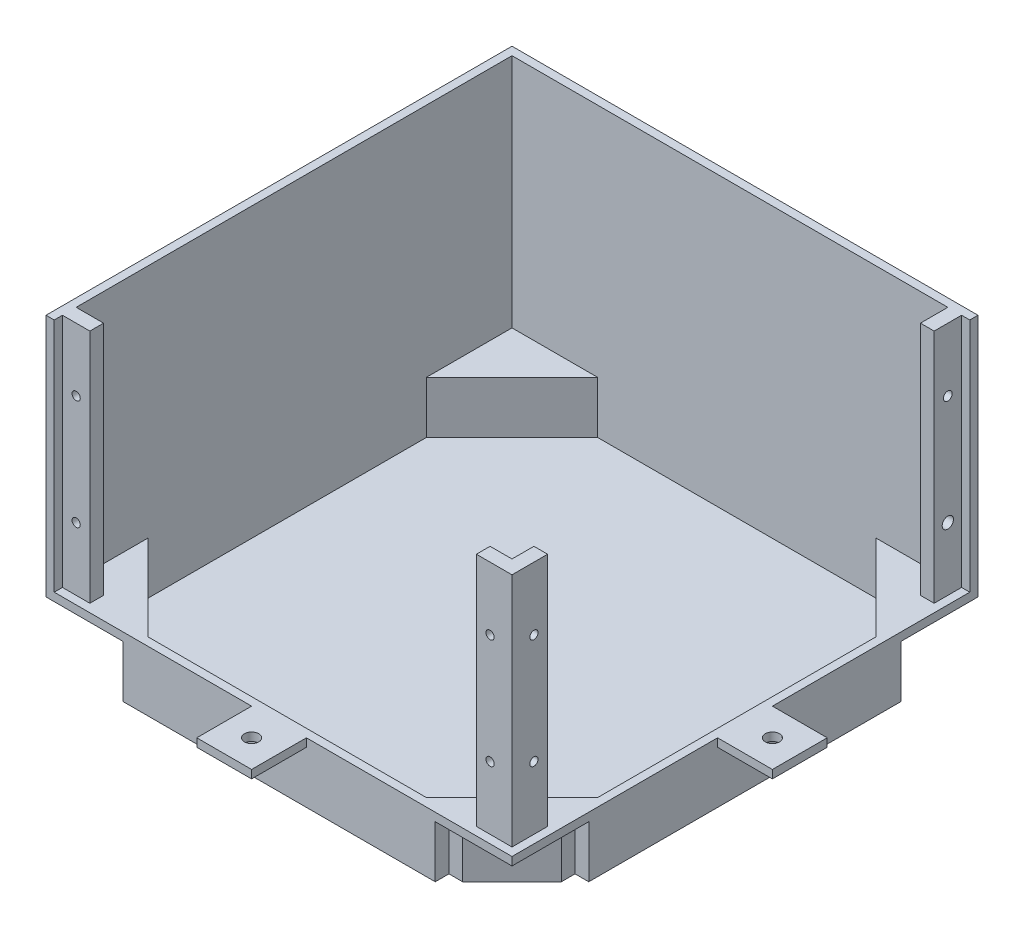
SolidWorks part; units mm, degrees
ref_plane "前视基准面" through (0, 0, 0) normal (0, 0, 1) x (1, 0, 0)
ref_plane "上视基准面" through (0, 0, 0) normal (0, 1, 0) x (1, 0, 0)
ref_plane "右视基准面" through (0, 0, 0) normal (1, 0, 0) x (0, 0, -1)
other "Configuration Table"
sketch "草图1" plane through (0, 0, 0) normal (0, 1, 0) x (1, 0, 0)
  line L21 (-80, 62) -> (-62, 80)
  line L23 (-85, 57) -> (-85, -57)
  line L26 (-85, 57) -> (-80, 57)
  line L27 (-80, 57) -> (-80, 62)
  line L28 (-57, 85) -> (-57, 80)
  line L30 (85, 57) -> (80, 57)
  line L31 (80, 57) -> (80, 62)
  line L33 (85, -57) -> (80, -57)
  line L34 (80, -57) -> (80, -62)
  line L37 (-85, -57) -> (-80, -57)
  line L38 (-80, -57) -> (-80, -62)
  line L39 (-57, 80) -> (-62, 80)
  line L40 (-57, 85) -> (57, 85)
  line L42 (57, 85) -> (57, 80)
  line L43 (57, 80) -> (62, 80)
  line L44 (62, 80) -> (80, 62)
  line L45 (-57, -85) -> (-57, -80)
  line L46 (-57, -80) -> (-62, -80)
  line L47 (57, -85) -> (57, -80)
  line L48 (57, -80) -> (62, -80)
  line L49 (-80, -62) -> (-62, -80)
  line L50 (85, 57) -> (85, -57)
  line L51 (62, -80) -> (80, -62)
  line L52 (-57, -85) -> (57, -85)
extrude "凸台-拉伸1" add sketch "草图1" along normal blind 4 contours L50 L33 L34 L51 L48 L47 L52 L45 L46 L49 L38 L37 L23 L26 L27 L21 L39 L28 L40 L42 L43 L44 L31 L30
sketch "草图2" plane through (0, 4, 0) normal (0, 1, 0) x (1, 0, 0)
  line L0 (-57, 85) -> (57, 85)
  line L1 (57, 85) -> (57, 80)
  line L2 (57, 80) -> (62, 80)
  line L3 (62, 80) -> (80, 62)
  line L4 (80, 62) -> (80, 57)
  line L5 (80, 57) -> (85, 57)
  line L6 (85, 57) -> (85, -57)
  line L7 (85, -57) -> (80, -57)
  line L8 (80, -57) -> (80, -62)
  line L9 (80, -62) -> (62, -80)
  line L10 (62, -80) -> (57, -80)
  line L11 (57, -80) -> (57, -85)
  line L12 (57, -85) -> (-57, -85)
  line L13 (-57, -85) -> (-57, -80)
  line L14 (-57, -80) -> (-62, -80)
  line L15 (-62, -80) -> (-80, -62)
  line L16 (-80, -62) -> (-80, -57)
  line L17 (-80, -57) -> (-85, -57)
  line L18 (-85, -57) -> (-85, 57)
  line L19 (-85, 57) -> (-80, 57)
  line L20 (-80, 57) -> (-80, 62)
  line L21 (-80, 62) -> (-62, 80)
  line L22 (-62, 80) -> (-57, 80)
  line L23 (-57, 80) -> (-57, 85)
  line L24 (-82, 50.7574) -> (-50.7574, 82)
  line L25 (50.7574, 82) -> (82, 50.7574)
  line L26 (50.7574, -82) -> (82, -50.7574)
  line L28 (-82, 50.7574) -> (-82, -50.7574)
  line L29 (50.7574, 82) -> (-50.7574, 82)
  line L30 (-82, -50.7574) -> (-50.7574, -82)
  line L31 (82, 50.7574) -> (82, -50.7574)
  line L32 (-50.7574, -82) -> (50.7574, -82)
extrude "凸台-拉伸2" add sketch "草图2" along normal blind 16 contours L23 L0 L1 L2 L3 L4 L5 L6 L7 L8 L9 L10 L11 L12 L13 L14 L15 L16 L17 L18 L19 L20 L21 L22 | L26 L31 L25 L29 L24 L28 L30 L32
sketch "草图3" plane through (0, 0, 0) normal (0, -1, 0) x (-1, 0, 0)
  line L0 (57, -85) -> (85, -85)
  line L1 (-57, 85) -> (-85, 85)
  line L3 (85, -85) -> (-85, -85)
  line L4 (85, -85) -> (85, 85)
  line L5 (85, 85) -> (-85, 85)
  line L6 (-85, -85) -> (-85, 85)
extrude "切除-拉伸2" cut sketch "草图3" against normal blind 1 contours L4 L3 L6 L5
sketch "草图4" plane through (0, 20, 0) normal (0, 1, 0) x (1, 0, 0)
  line L0 (-57, 85) -> (-85, 85)
  line L1 (57, -85) -> (85, -85)
  line L3 (-85, 85) -> (85, 85)
  line L4 (-85, 85) -> (-85, -85)
  line L5 (-85, -85) -> (85, -85)
  line L6 (85, 85) -> (85, -85)
  line M31 (82, -50.7574) -> (50.7574, -82)
  line M32 (50.7574, -82) -> (-50.7574, -82)
  line M33 (-50.7574, -82) -> (-82, -50.7574)
  line M34 (-82, -50.7574) -> (-82, 50.7574)
  line M35 (-82, 50.7574) -> (-50.7574, 82)
  line M36 (-50.7574, 82) -> (50.7574, 82)
  line M37 (50.7574, 82) -> (82, 50.7574)
  line M38 (82, 50.7574) -> (82, -50.7574)
extrude "凸台-拉伸3" add sketch "草图4" along normal blind 3 contours M31 M38 M37 M36 M35 M34 M33 M32 | L4 L3 L6 L5 region at (0, 20, 0)
sketch "草图5" plane through (0, 23, 0) normal (0, 1, 0) x (1, 0, 0)
  line L0 (85, 85) -> (85, -85) construction
  line L1 (-85, 85) -> (85, 85)
  line L2 (-85, 85) -> (-85, 82)
  line L3 (-85, 82) -> (85, 82)
  line L4 (85, 85) -> (85, 82)
  line L6 (-85, -85) -> (-82, -85)
  line L7 (-85, -85) -> (-85, 82)
  line L8 (-85, 82) -> (-82, 82)
  line L9 (-82, -85) -> (-82, 82)
  line M13 (-82, -50.7574) -> (-82, 50.7574)
  line M15 (-50.7574, 82) -> (50.7574, 82)
  line M17 (-85, -85) -> (85, -85)
  line M18 (85, -85) -> (85, 85)
  line M19 (85, 85) -> (-85, 85)
  line M20 (-85, 85) -> (-85, -85)
extrude "凸台-拉伸4" add sketch "草图5" along normal blind 86 contours L3 M20 M15 M18 M19 | L9 L3 M17 M13 M20 region at (0, 23, -83.5) region at (-83.5, 23, 1.5)
sketch "草图7" plane through (0, 23, 0) normal (0, 1, 0) x (1, 0, 0)
  line L1 (-82, -85) -> (-82, 82) construction
  line L2 (-82, -82) -> (-82, -79)
  line L3 (-82, -85) -> (-82, -50.7574) construction
  line L8 (50.7574, 82) -> (85, 82) construction
  line L9 (82, 82) -> (79, 82)
  line L13 (-82, -79) -> (-72, -79)
  line L14 (-72, -79) -> (-72, -82)
  line L15 (-82, -82) -> (-72, -82)
  line L16 (82, 82) -> (82, 72)
  line L17 (82, 72) -> (79, 72)
  line L18 (79, 82) -> (79, 72)
  line L19 (50.7574, -82) -> (82, -82)
  line L20 (82, -82) -> (82, -50.7574)
  line L22 (82, -82) -> (79, -82)
  line L23 (82, -82) -> (82, -72)
  line L24 (82, -72) -> (79, -72)
  line L25 (79, -82) -> (79, -72)
  line L26 (82, -82) -> (72, -82)
  line L27 (82, -82) -> (82, -79)
  line L28 (82, -79) -> (72, -79)
  line L29 (72, -82) -> (72, -79)
  line M9 (85, 82) -> (50.7574, 82)
  line M15 (-82, -50.7574) -> (-82, -85)
extrude "凸台-拉伸6" add sketch "草图7" along normal blind 86 contours L15 L14 L13 M15 | L28 L23 L24 L25 | L20 L28 L25 L19 | L29 L19 L25 L28 | L18 L17 L16 M9 region at (-77, 23, 80.5) region at (80.5, 23, -77) region at (75.5, 23, 80.5) region at (80.5, 23, 80.5) region at (80.5, 23, 75.5)
sketch "草图8" plane through (0, 0, 82) normal (0, 0, 1) x (1, 0, 0)
  line L0 (-72, 109) -> (-72, 23)
  line L1 (-72, 66) -> (-77, 66)
  line L2 (-77, 66) -> (-77, 86)
  line L3 (-77, 66) -> (-77, 46)
  line L4 (-77, 86) -> (77, 86)
  line L5 (-77, 46) -> (77, 46)
  circle A0 centre (-77, 86) radius 1.5
  circle A1 centre (-77, 46) radius 1.5
extrude "切除-拉伸3" cut sketch "草图8" against normal blind 86 contours L4 A0 L2 | L2 A0 L4 | L5 A1 L3 | L3 A1 L5 region at (-76.3634, 85.3634, 82) region at (-77.2122, 86.2122, 82) region at (-77.2122, 45.7878, 82) region at (-76.3634, 46.6366, 82)
sketch "草图9" plane through (82, 0, 0) normal (1, 0, 0) x (0, 0, -1)
  line L0 (72, 109) -> (72, 23)
  line L1 (72, 66) -> (82, 66)
  line L2 (82, 109) -> (82, 23) construction
  line L3 (77, 66) -> (77, 86)
  line L4 (77, 66) -> (77, 46)
  line L5 (77, 46) -> (-77, 46)
  line L8 (77, 86) -> (-77, 86)
  circle A0 centre (77, 86) radius 1.6062
  circle A1 centre (77, 46) radius 2.0555
extrude "切除-拉伸4" cut sketch "草图9" against normal blind 86 contours L3 A0 L8 | L8 A0 L3 | L5 A1 L4 | L4 A1 L5 region at (82, 86.2272, -77.2272) region at (82, 85.3183, -76.3183) region at (82, 46.8724, -76.1276) region at (82, 45.7092, -77.2908)
sketch "草图10" plane through (0, 109, 0) normal (0, 1, 0) x (1, 0, 0)
  line L1 (79, -72) -> (82, -72)
  line L2 (79, -72) -> (79, -69)
  line L3 (79, -69) -> (82, -69)
  line L4 (82, -72) -> (82, -69)
  line L5 (72, -82) -> (69, -82)
  line L6 (72, -82) -> (72, -79)
  line L7 (72, -79) -> (69, -79)
  line L8 (69, -82) -> (69, -79)
extrude "凸台-拉伸7" add sketch "草图10" against normal blind 86
sketch "草图11" plane through (0, 0, 82) normal (0, 0, 1) x (1, 0, 0)
  line L0 (-77, 86) -> (69, 86)
  line L1 (69, 23) -> (69, 109) construction
  line L2 (69, 86) -> (74, 86)
  line L3 (74, 86) -> (74, 46)
  circle A2 centre (74, 86) radius 1.5
  circle A3 centre (74, 46) radius 1.5
extrude "切除-拉伸5" cut sketch "草图11" against normal blind 86 contours L3 A2 L2 | L2 A2 L3 | A3 region at (74.2122, 86.2122, 82) region at (75.0307, 47.0307, 82) region at (73.3634, 85.3634, 82)
sketch "草图12" plane through (0, 109, 0) normal (0, 1, 0) x (1, 0, 0)
  line L0 (79, -79) -> (79, -69) construction
  line L1 (69, -79) -> (79, -79)
  line L2 (69, -79) -> (69, -77)
  line L3 (69, -77) -> (79, -77)
  line L4 (79, -79) -> (79, -77)
  line L6 (79, -69) -> (77, -69)
  line L7 (79, -69) -> (79, -77)
  line L8 (79, -77) -> (77, -77)
  line L9 (77, -69) -> (77, -77)
  line M9 (79, -69) -> (79, -79)
  line M10 (79, -79) -> (69, -79)
extrude "凸台-拉伸8" add sketch "草图12" against normal blind 86 contours L6 L9 L3 M9 | L3 L2 M10 M9 region at (74, 109, 78) region at (78, 109, 73)
sketch "草图13" plane through (0, 0, 82) normal (0, 0, 1) x (1, 0, 0)
  circle A0 centre (74, 86) radius 1.5
  circle A1 centre (74, 46) radius 1.5
extrude "切除-拉伸6" cut sketch "草图13" against normal blind 86
sketch "草图14" plane through (0, 0, 77) normal (0, 0, -1) x (-1, 0, 0)
  circle A0 centre (-74, 86) radius 3
  circle A1 centre (-74, 46) radius 3
extrude "切除-拉伸7" cut sketch "草图14" against normal blind 2
sketch "草图15" plane through (82, 0, 0) normal (1, 0, 0) x (0, 0, -1)
  line L0 (77, 86) -> (-69, 86)
  line L1 (-69, 23) -> (-69, 109) construction
  line L2 (-69, 86) -> (-74, 86)
  line L3 (-74, 86) -> (-74, 46)
  circle A0 centre (-74, 86) radius 1.5
  circle A1 centre (-74, 46) radius 1.5
extrude "切除-拉伸8" cut sketch "草图15" against normal blind 5 contours L2 A0 L3 | L3 A0 L2 | A1 region at (82, 85.3634, 73.3634) region at (82, 86.2122, 74.2122) region at (82, 47.0307, 72.9693)
sketch "草图16" plane through (77, 0, 0) normal (-1, 0, 0) x (0, 0, 1)
  circle A0 centre (74, 86) radius 3
  circle A1 centre (74, 46) radius 3
extrude "切除-拉伸9" cut sketch "草图16" against normal blind 2
sketch "草图17" plane through (0, 109, 0) normal (0, 1, 0) x (1, 0, 0)
  line L0 (-82, -79) -> (-82, -50.7574) construction
  line L1 (-72, -79) -> (-82, -79)
  line L2 (-72, -79) -> (-72, -77)
  line L3 (-72, -77) -> (-82, -77)
  line L4 (-82, -79) -> (-82, -77)
  line L5 (50.7574, 82) -> (79, 82) construction
  line L6 (79, 72) -> (77, 72)
  line L7 (79, 72) -> (79, 82)
  line L8 (79, 82) -> (77, 82)
  line L9 (77, 72) -> (77, 82)
extrude "凸台-拉伸9" add sketch "草图17" against normal blind 86
sketch "草图18" plane through (77, 0, 0) normal (-1, 0, 0) x (0, 0, 1)
  line L0 (-72, 66) -> (-77, 66)
  line L1 (-72, 23) -> (-72, 109) construction
  line L2 (-77, 66) -> (-77, 86)
  line L3 (-77, 66) -> (-77, 46)
  circle A0 centre (-77, 86) radius 3
  circle A1 centre (-77, 46) radius 3
extrude "切除-拉伸10" cut sketch "草图18" against normal blind 2 contours A0 | A1 region at (77, 88.0613, -79.0613) region at (77, 48.0613, -74.9387)
sketch "草图19" plane through (0, 0, 77) normal (0, 0, -1) x (-1, 0, 0)
  line L0 (72, 66) -> (82, 66)
  line L1 (72, 23) -> (72, 109) construction
  line L2 (82, 23) -> (82, 109) construction
  line L3 (77, 66) -> (77, 86)
  line L4 (77, 66) -> (77, 46)
  circle A0 centre (77, 86) radius 3
  circle A1 centre (77, 46) radius 3
extrude "切除-拉伸11" cut sketch "草图19" against normal blind 2 contours A0 | A1 region at (-74.9387, 88.0613, 77) region at (-79.0613, 48.0613, 77)
sketch "草图22" plane through (0, 23, 0) normal (0, 1, 0) x (1, 0, 0)
  line L0 (0, 0) -> (85, 0)
  line L2 (85, 82) -> (85, -85) construction
  line L3 (0, 0) -> (-85, 0)
  line L4 (105, 0) -> (105, 10)
  line L9 (85, 0) -> (85, -10)
  line L10 (0, 0) -> (0, -85)
  line L11 (85, -10) -> (105, -10)
  line L12 (85, -10) -> (85, 10)
  line L13 (85, 10) -> (105, 10)
  line L14 (105, -10) -> (105, 10)
  line L15 (-82, -85) -> (85, -85) construction
  line L16 (-85, 85) -> (-85, -85) construction
  line L17 (0, -105) -> (10, -105)
  line L18 (0, -85) -> (-10, -85)
  line L19 (-85, 0) -> (-105, 0)
  line L20 (-10, -85) -> (10, -85)
  line L21 (-10, -85) -> (-10, -105)
  line L22 (-10, -105) -> (10, -105)
  line L23 (10, -85) -> (10, -105)
  line L24 (-105, 0) -> (-105, 20)
  line L25 (-105, 20) -> (-85, 20)
  line L26 (-85, 20) -> (-85, 0)
  circle A1 centre (0, -95) radius 2.6
  circle A2 centre (95, 0) radius 2.6
  circle A3 centre (-95, 10) radius 2.6
  line M47 (-82, -85) -> (85, -85)
  line M48 (85, -85) -> (85, 82)
extrude "凸台-拉伸10" add sketch "草图22" against normal blind 3 contours L26 L25 L24 L19 A3 | L23 L21 L22 L17 A1 M47 | L11 L14 L4 L13 A2 M48 region at (-95, 23, -0.2828) region at (85.2828, 23, -5) region at (5, 23, 85.2828)
